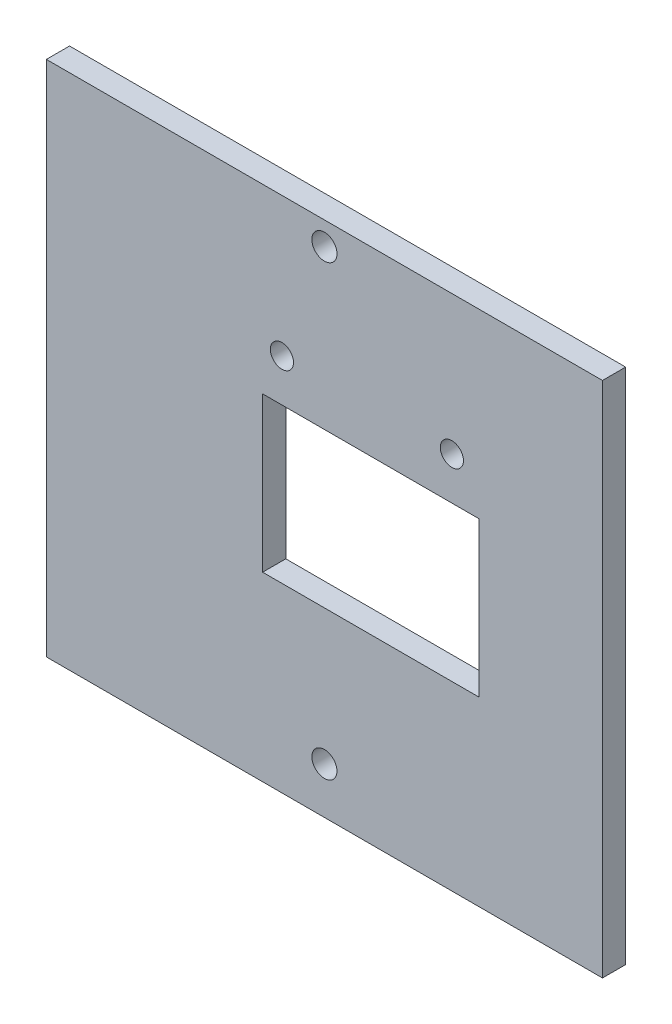
SolidWorks part; units mm, degrees
ref_plane "Alzado" through (0, 0, 0) normal (0, 0, 1) x (1, 0, 0)
ref_plane "Planta" through (0, 0, 0) normal (0, 1, 0) x (1, 0, 0)
ref_plane "Vista lateral" through (0, 0, 0) normal (1, 0, 0) x (0, 0, -1)
sketch "Croquis1" plane through (0, 0, 0) normal (0, 0, 1) x (1, 0, 0)
  line B0 (47.0497, -53.14) -> (47.0497, 13.86)
  line B1 (47.0497, 13.86) -> (119.0497, 13.86)
  line B2 (47.0497, -53.14) -> (119.0497, -53.14)
  line B3 (119.0497, -53.14) -> (119.0497, 13.86)
sketch_block_instance "Bloque-Croquis2-1"
sketch_block "Bloque-Croquis2" parameters "D1"=50, "D2"=59.9093
extrude "Saliente-Extruir1" add sketch "Croquis1" along normal blind 3
sketch "Croquis4" plane through (0, 0, 0) normal (0, 0, -1) x (-1, 0, 0)
  line L0 (-78.0497, -9.64) -> (-75.0497, -9.64)
  line L2 (-78.0497, -9.64) -> (-78.0497, -29.64) construction
  line L3 (-78.0497, -29.64) -> (-103.0497, -29.64)
  line L4 (-103.0497, -9.64) -> (-103.0497, -29.64)
  line L5 (-119.0497, -53.14) -> (-119.0497, 13.86) construction
  line L6 (-47.0497, -53.14) -> (-119.0497, -53.14) construction
  line L11 (-103.0497, -9.64) -> (-78.0497, -9.64)
  line L12 (-103.0497, -9.64) -> (-103.0497, -4.14) construction
  line L13 (-103.0497, -4.14) -> (-78.0497, -4.14) construction
  line L14 (-78.0497, -9.64) -> (-78.0497, -4.14) construction
  line L15 (-75.0497, -9.64) -> (-75.0497, -29.64)
  line L16 (-75.0497, -29.64) -> (-78.0497, -29.64)
  circle A0 centre (-83.0497, -47.14) radius 1.625 construction
  circle A1 centre (-83.0497, 10.86) radius 1.625 construction
  circle A2 centre (-83.0497, -47.14) radius 1.625
  circle A3 centre (-83.0497, 10.86) radius 1.625
  circle A4 centre (-99.5497, -4.14) radius 1.5
  circle A5 centre (-77.5497, -4.14) radius 1.5
  dimension "D6" = 3
  dimension "D7" = 3
  dimension "D8" = 3.5
  dimension "D9" = 0.5
  dimension "D1" = 16
  dimension "D2" = 23.5
  dimension "D3" = 25
  dimension "D4" = 20
  dimension "D5" = 5.5
  dimension "D10" = 3
extrude "Cortar-Extruir2" cut sketch "Croquis4" against normal blind 3
sketch "Croquis5" plane through (0, 0, 0) normal (0, 0, -1) x (-1, 0, 0)
  line L0 (-103.0497, -29.64) -> (-75.0497, -29.64) construction
  line L1 (-75.0497, -9.64) -> (-78.0497, -9.64) construction
  line L2 (-75.0497, -9.64) -> (-75.0497, -29.64) construction
  line L3 (-75.0497, -29.64) -> (-78.0497, -29.64) construction
  line L4 (-78.0497, -9.64) -> (-78.0497, -29.64)
  line L5 (-75.0497, -9.64) -> (-103.0497, -9.64) construction
  line L6 (-101.0497, -28.64) -> (-82.0497, -28.64)
  line L7 (-101.0497, -28.64) -> (-101.0497, -10.64)
  line L8 (-101.0497, -10.64) -> (-82.0497, -10.64)
  line L9 (-82.0497, -28.64) -> (-82.0497, -10.64)
  line L12 (-103.0497, -9.64) -> (-103.0497, -29.64) construction
  point P16 (0, 0)
  dimension "D1" = 3
  dimension "D2" = 1
  dimension "D3" = 2
  dimension "D4" = 19
  dimension "D5" = 18
sketch "Sketch1" plane through (0, 0, 0) normal (0, 0, -1) x (-1, 0, 0)
  line L0 (-83.1641, -11.7027) -> (-83.0942, -11.8472)
  line L1 (-83.0942, -11.8472) -> (-83.0948, -18.3285)
  line L2 (-84.5101, -22.6163) -> (-84.3138, -22.7155)
  line L3 (-84.3138, -22.7155) -> (-84.3138, -19.1831)
  line L4 (-84.3138, -19.1831) -> (-84.3138, -15.6507)
  line L5 (-84.3138, -15.6507) -> (-84.4209, -15.6685)
  line L6 (-93.8632, -16.7274) -> (-93.9366, -16.7434)
  line L7 (-93.9366, -16.7434) -> (-93.9457, -21.4694)
  spline S0 degree 3 poles (-97.4813, -28.221) (-98.4589, -28.08) (-99.3683, -27.4918) (-99.7346, -26.7635) knots 0 0 0 0 1 1 1 1
  spline S1 degree 3 poles (-99.7346, -26.7635) (-99.8636, -26.507) (-99.97, -26.0939) (-99.9692, -25.852) knots 0 0 0 0 1 1 1 1
  spline S2 degree 3 poles (-99.9692, -25.852) (-99.9676, -25.3544) (-99.7498, -24.8284) (-99.3776, -24.4241) knots 0 0 0 0 1 1 1 1
  spline S3 degree 3 poles (-99.3776, -24.4241) (-98.4364, -23.4016) (-96.6968, -23.1394) (-95.3585, -23.8183) knots 0 0 0 0 1 1 1 1
  spline S4 degree 3 poles (-95.3585, -23.8183) (-95.2673, -23.8645) (-95.1849, -23.9023) (-95.1752, -23.9023) knots 0 0 0 0 1 1 1 1
  spline S5 degree 3 poles (-95.1752, -23.9023) (-95.1655, -23.9023) (-95.1575, -21.4859) (-95.1574, -18.5325) knots 0 0 0 0 1 1 1 1
  spline S6 degree 3 poles (-95.1574, -18.5325) (-95.1573, -14.7522) (-95.1466, -13.1236) (-95.1212, -13.0307) knots 0 0 0 0 1 1 1 1
  spline S7 degree 3 poles (-95.1212, -13.0307) (-95.0718, -12.8494) (-94.9575, -12.7079) (-94.8066, -12.641) knots 0 0 0 0 1 1 1 1
  spline S8 degree 3 poles (-94.8066, -12.641) (-94.6483, -12.5709) (-83.7693, -11.3493) (-83.5886, -11.3814) knots 0 0 0 0 1 1 1 1
  spline S9 degree 3 poles (-83.5886, -11.3814) (-83.4121, -11.4128) (-83.2421, -11.5414) (-83.1641, -11.7027) knots 0 0 0 0 1 1 1 1
  spline S10 degree 3 poles (-83.0948, -18.3285) (-83.0955, -25.551) (-83.0792, -25.0483) (-83.3288, -25.5448) knots 0 0 0 0 1 1 1 1
  spline S11 degree 3 poles (-83.3288, -25.5448) (-83.7851, -26.4524) (-84.8745, -27.0368) (-86.1101, -27.0368) knots 0 0 0 0 1 1 1 1
  spline S12 degree 3 poles (-86.1101, -27.0368) (-86.7692, -27.0368) (-87.3291, -26.8912) (-87.8938, -26.5729) knots 0 0 0 0 1 1 1 1
  spline S13 degree 3 poles (-87.8938, -26.5729) (-88.2002, -26.4002) (-88.6579, -25.9603) (-88.8215, -25.6814) knots 0 0 0 0 1 1 1 1
  spline S14 degree 3 poles (-88.8215, -25.6814) (-89.3109, -24.847) (-89.1755, -23.8724) (-88.4706, -23.1558) knots 0 0 0 0 1 1 1 1
  spline S15 degree 3 poles (-88.4706, -23.1558) (-87.5017, -22.1709) (-85.8395, -21.9445) (-84.5101, -22.6163) knots 0 0 0 0 1 1 1 1
  spline S16 degree 3 poles (-84.4209, -15.6685) (-84.4798, -15.6783) (-86.6119, -15.917) (-89.1589, -16.1989) knots 0 0 0 0 1 1 1 1
  spline S17 degree 3 poles (-89.1589, -16.1989) (-91.7059, -16.4808) (-93.8228, -16.7186) (-93.8632, -16.7274) knots 0 0 0 0 1 1 1 1
  spline S18 degree 3 poles (-93.9457, -21.4694) (-93.9544, -25.9747) (-93.9577, -26.2039) (-94.0161, -26.3769) knots 0 0 0 0 1 1 1 1
  spline S19 degree 3 poles (-94.0161, -26.3769) (-94.2438, -27.0516) (-94.702, -27.5543) (-95.3997, -27.895) knots 0 0 0 0 1 1 1 1
  spline S20 degree 3 poles (-95.3997, -27.895) (-96.0298, -28.2027) (-96.7866, -28.3212) (-97.4813, -28.221) knots 0 0 0 0 1 1 1 1
  point P0 (0, 0)
